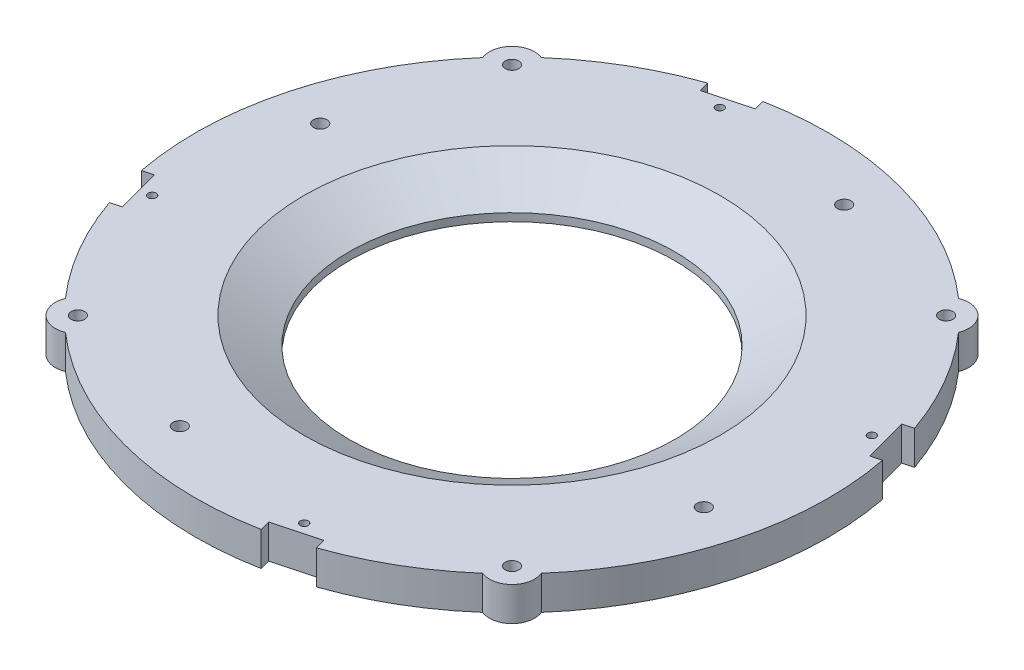
SolidWorks part; units mm, degrees
material "6061-T6 (SS)"
ref_plane "Front Plane" through (0, 0, 0) normal (0, 0, 1) x (1, 0, 0)
ref_plane "Top Plane" through (0, 0, 0) normal (0, 1, 0) x (1, 0, 0)
ref_plane "Right Plane" through (0, 0, 0) normal (1, 0, 0) x (0, 0, -1)
sketch "Sketch1" plane through (0, 0, 0) normal (0, 1, 0) x (1, 0, 0)
  line L0 (0, 88.9) -> (0, -88.9) construction
  line L1 (-88.9, 0) -> (88.9, 0) construction
  line L2 (-60.9759, -60.9759) -> (60.9759, 60.9759) construction
  line L3 (60.9759, -60.9759) -> (-60.9759, 60.9759) construction
  arc A0 (-66.8608, 58.5904) -> (-66.8608, -58.5904) centre (0, 0) ccw
  arc A1 (-58.5904, 66.8608) -> (-66.8608, 58.5904) centre (-60.9759, 60.9759) ccw
  arc A2 (66.8608, 58.5904) -> (58.5904, 66.8608) centre (60.9759, 60.9759) ccw
  arc A3 (58.5904, -66.8608) -> (66.8608, -58.5904) centre (60.9759, -60.9759) ccw
  arc A4 (-66.8608, -58.5904) -> (-58.5904, -66.8608) centre (-60.9759, -60.9759) ccw
  arc A5 (58.5904, 66.8608) -> (-58.5904, 66.8608) centre (0, 0) ccw
  arc A6 (66.8608, -58.5904) -> (66.8608, 58.5904) centre (0, 0) ccw
  arc A7 (-58.5904, -66.8608) -> (58.5904, -66.8608) centre (0, 0) ccw
  circle A8 centre (-60.9759, 60.9759) radius 1.905
  circle A9 centre (60.9759, 60.9759) radius 1.905
  circle A10 centre (60.9759, -60.9759) radius 1.905
  circle A11 centre (-60.9759, -60.9759) radius 1.905
  circle A12 centre (0, 0) radius 83.82 construction
  point P10 (0, 0)
  point P13 (0, 0)
  dimension "D1" = 177.8
  dimension "D3" = 12.7
  dimension "D4" = 3.81
  dimension "D7" = 167.64
  dimension "D2" = 90
  dimension "D5" = 45
  dimension "D6" = 172.466
extrude "Boss-Extrude1" add sketch "Sketch1" along normal blind 9.525
sketch "Sketch2" plane through (0, 9.525, 0) normal (0, 1, 0) x (1, 0, 0)
  circle A0 centre (0, 0) radius 45.72
extrude "Cut-Extrude1" cut sketch "Sketch2" against normal blind 12.7
sketch "Sketch4" plane through (0, 9.525, 0) normal (0, 1, 0) x (1, 0, 0)
  line L0 (0, 0) -> (19.722, 73.6035) construction
  line L2 (0, 0) -> (0, 123.2999) construction
  circle A0 centre (19.722, 73.6035) radius 1.905
  dimension "D1" = 3.81
  dimension "D2" = 76.2
  dimension "D3" = 345
ref_plane "Plane3" through (-62.8618, 0, -62.8618) normal (-0.7071, 0, -0.7071) x (0, -1, 0)
sketch "Sketch10" plane through (-62.8618, 0, -62.8618) normal (-0.7071, 0, -0.7071) x (0, -1, 0)
  line L0 (0, 0) -> (-9.652, 0) construction
  circle A1 centre (-4.826, 0) radius 0.6985
  dimension "D2" = 1.397
  dimension "D1" = 9.652
extrude "Cut-Extrude5" cut sketch "Sketch10" against normal blind 3.175
pattern_circular "CirPattern5" count 4 over 360 about axis through (0, 9.525, 0) along (0, 1, 0) of "Cut-Extrude5"
chamfer "Chamfer1" distance 12.7 angle 30 1 edges at (0, 9.525, 45.72) first distance on face at (0, 9.525, 45.72)
extrude "Cut-Extrude6" cut sketch "Sketch4" against normal through all
pattern_circular "CirPattern6" count 4 over 360 about axis through (0, 9.525, 0) along (0, 1, 0) of "Cut-Extrude6"
sketch "Sketch13" plane through (0, 9.525, 0) normal (0, 1, 0) x (1, 0, 0)
  line L0 (0, 0) -> (0, 128.7148) construction
  line L1 (0, 0) -> (-35.1918, 131.3375) construction
  circle A0 centre (-21.3655, 79.7372) radius 1.1303
  dimension "D3" = 2.2606
  dimension "D1" = 345
  dimension "D2" = 82.55
extrude "Cut-Extrude7" cut sketch "Sketch13" against normal through all
pattern_circular "CirPattern7" count 4 over 360 about axis through (0, 9.525, 0) along (0, 1, 0) of "Cut-Extrude7"
ref_plane "Plane4" through (-23.009, 0, -85.8708) normal (-0.2588, 0, -0.9659) x (0, -1, 0)
sketch "Sketch14" plane through (-23.009, 0, -85.8708) normal (-0.2588, 0, -0.9659) x (0, -1, 0)
  line L1 (1.3545, -6.35) -> (-10.5978, -6.35)
  line L2 (1.3545, -6.35) -> (1.3545, 6.35)
  line L3 (1.3545, 6.35) -> (-10.5978, 6.35)
  line L4 (-10.5978, -6.35) -> (-10.5978, 6.35)
  line L5 (1.3545, -6.35) -> (-10.5978, 6.35) construction
  line L6 (1.3545, 6.35) -> (-10.5978, -6.35) construction
  point P0 (-4.6217, 0)
  dimension "D1" = 12.7
extrude "Cut-Extrude8" cut sketch "Sketch14" against normal blind 3.175
pattern_circular "CirPattern8" count 4 over 360 about axis through (0, 9.525, 0) along (0, 1, 0) of "Cut-Extrude8"
